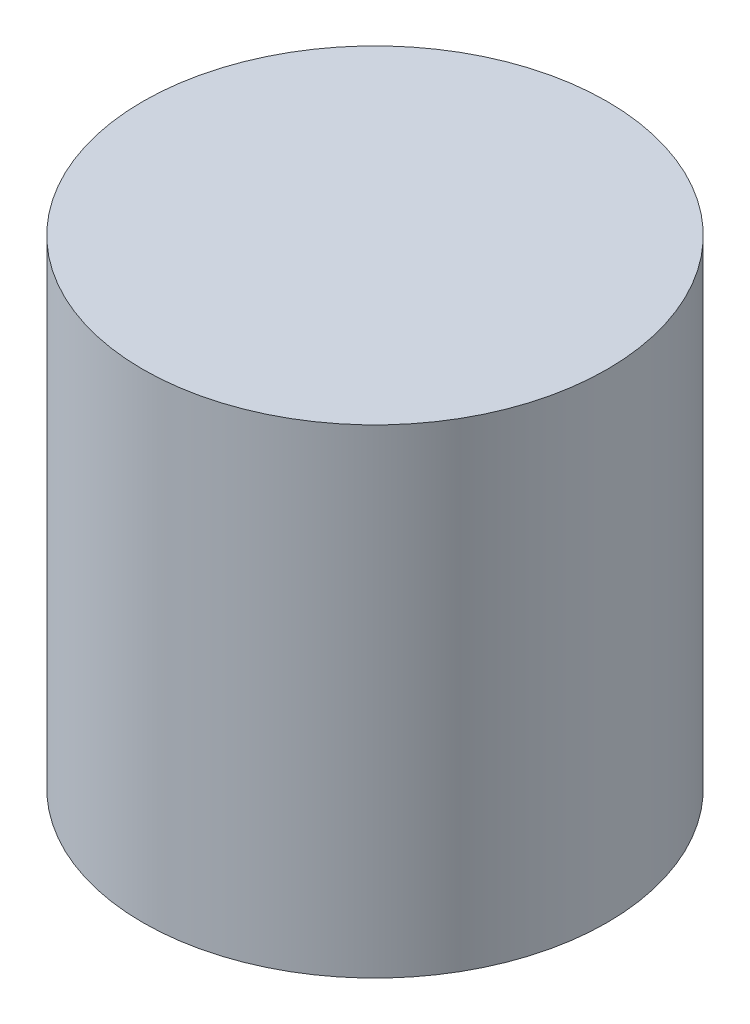
SolidWorks part; units mm, degrees
ref_plane "Спереди" through (0, 0, 0) normal (0, 0, 1) x (1, 0, 0)
ref_plane "Сверху" through (0, 0, 0) normal (0, 1, 0) x (1, 0, 0)
ref_plane "Справа" through (0, 0, 0) normal (1, 0, 0) x (0, 0, -1)
sketch "Эскиз1" plane through (0, 0, 0) normal (0, 1, 0) x (1, 0, 0)
  circle A0 centre (0, 0) radius 10
  dimension "D1" = 20
extrude "Бобышка-Вытянуть1" add sketch "Эскиз1" against normal blind 20.64
ref_plane "face_for_mating" through (0, 0, 0) normal (0, 1, 0) x (1, 0, 0)
ref_plane "face_for_horizont" through (0, -20.64, 0) normal (0, -1, 0) x (-1, 0, 0)
equation "\"H\"=7+10.26+3.38"
equation "\"D\"=20"
equation "\"D1@Эскиз1\" = \"D\""
equation "\"D1@Бобышка-Вытянуть1\" = \"H\""
